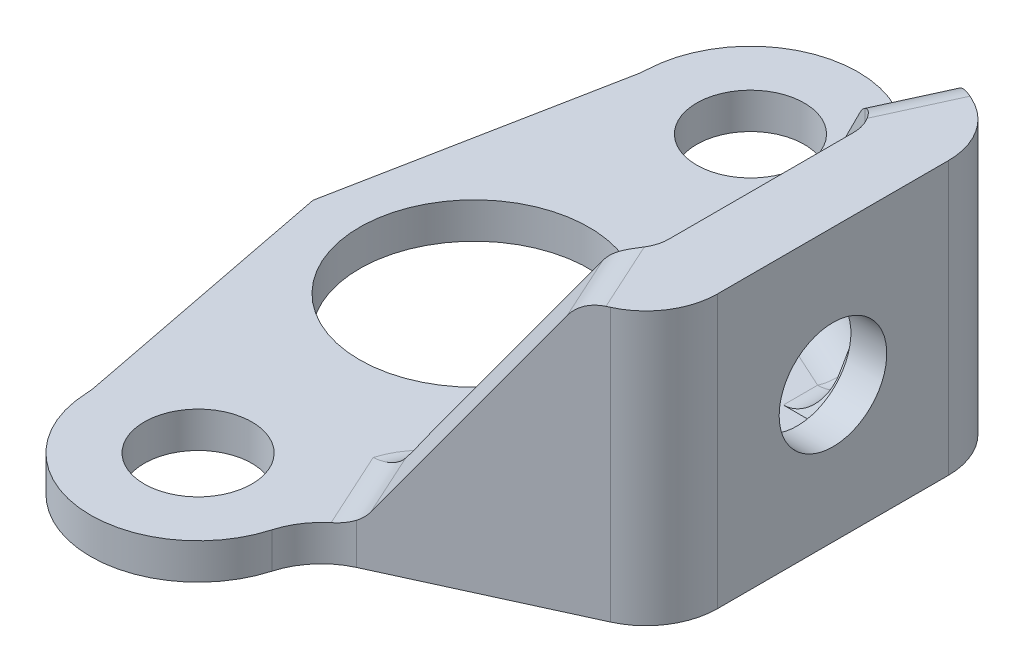
SolidWorks part; units mm, degrees
ref_plane "Plan de face" through (0, 0, 0) normal (0, 0, 1) x (1, 0, 0)
ref_plane "Plan de dessus" through (0, 0, 0) normal (0, 1, 0) x (1, 0, 0)
ref_plane "Plan de droite" through (0, 0, 0) normal (1, 0, 0) x (0, 0, -1)
sketch "Esquisse1" plane through (0, 0, 0) normal (0, 1, 0) x (1, 0, 0)
  line L0 (0, -1000) -> (0, 49000) construction
  line L1 (10, -999.2472) -> (10, 49000.7528) construction
  line L2 (-3.0322, 7.5348) -> (-4.5, 0)
  line L3 (-1000, 4.5) -> (49000, 4.5) construction
  line L4 (3.9764, 7.2537) -> (8.8315, 5.0342)
  line L5 (10, 3.2152) -> (10, -3.2152)
  line L6 (-1000, 0) -> (49000, 0) construction
  line L7 (3.9764, -7.2537) -> (8.8315, -5.0342)
  line L8 (-3.0322, -7.5348) -> (-4.5, 0)
  line L9 (8, 2.5728) -> (8, -2.5728)
  line L10 (7.4158, -3.4823) -> (4.0543, -5.0189)
  line L11 (7.4158, 3.4823) -> (4.0543, 5.0189)
  line L12 (3.9764, 7.2537) -> (3.5606, 6.3442)
  line L13 (3.5606, -6.3442) -> (3.9764, -7.2537)
  circle A0 centre (0, 0) radius 3.2
  circle A1 centre (0, 7.7) radius 1.5
  circle A2 centre (0, 7.7) radius 3 construction
  circle A3 centre (0, 0) radius 4.5 construction
  arc A4 (-2.9972, 7.8303) -> (2.8847, 8.5236) centre (0, 7.7) cw
  arc A5 (-2.9972, 7.8303) -> (-3.0322, 7.5348) centre (-4.9953, 7.9172) cw
  arc A6 (8.8315, 5.0342) -> (10, 3.2152) centre (8, 3.2152) cw
  arc A7 (2.8847, 8.5236) -> (3.9764, 7.2537) centre (4.8079, 9.0726) ccw
  circle A8 centre (0, -7.7) radius 1.5
  arc A9 (8.8315, -5.0342) -> (10, -3.2152) centre (8, -3.2152) ccw
  arc A10 (2.8847, -8.5236) -> (3.9764, -7.2537) centre (4.8079, -9.0726) cw
  arc A11 (-2.9972, -7.8303) -> (2.8847, -8.5236) centre (0, -7.7) ccw
  arc A12 (-2.9972, -7.8303) -> (-3.0322, -7.5348) centre (-4.9953, -7.9172) ccw
  arc A13 (4.0543, -5.0189) -> (3.5606, -6.3442) centre (4.4701, -5.9284) ccw
  arc A14 (8, -2.5728) -> (7.4158, -3.4823) centre (7, -2.5728) cw
  arc A15 (7.4158, 3.4823) -> (8, 2.5728) centre (7, 2.5728) cw
  arc A16 (4.0543, 5.0189) -> (3.5606, 6.3442) centre (4.4701, 5.9284) cw
  point P7 (0, 6.2)
  point P8 (0, 3.2)
  point P24 (10, 4.5)
  point P27 (3, 7.7)
  point P33 (10, 0)
  dimension "D1" = 6.4
  dimension "D3" = 3
  dimension "D4" = 6
  dimension "D5" = 9
  dimension "D7" = 2
  dimension "D9" = 1
  dimension "D2" = 3
  dimension "D6" = 10
  dimension "D8" = 2
extrude "Boss.-Extru.1" add sketch "Esquisse1" against normal blind 1 contours L11 A16 L12 A7 A4 A5 L2 L8 A12 A11 A10 L13 A13 L10 A14 L9 A15 A0 A1 A8 | A16 L11 A15 L9 A14 L10 A13 L13 L7 A9 L5 A6 L4 L12 region at (-2.7631, 0, -7.6528) region at (6.3378, 0, -5.9992)
extrude "Boss.-Extru.2" add sketch "Esquisse1<3>" along normal blind 6.6 contours A16 L11 A15 L9 A14 L10 A13 L13 L7 A9 L5 A6 L4 L12 region at (6.3378, 0, -5.9992)
sketch "Esquisse1<3>" plane through (0, 0, 0) normal (0, 1, 0) x (1, 0, 0) same geometry as "Esquisse1"
chamfer "Chanfrein1" distance 6.6 distance2 4.73 2 edges at (3.7685, 6.6, 6.7989) (3.7685, 6.6, -6.7989) tangent propagation no first distance on face at (3.7685, 3.3, 6.7989) first distance on face at (3.7685, 3.3, -6.7989)
fillet "Congé1" radius 1 9 edges at (7.8623, 6.6, 4.3774) (7.8623, 6.6, -4.3774) (3.7685, 0, 6.7989) (5.7351, 0, 4.2506) (7.8414, 0, 3.1133) (8, 0, 0) (7.8414, 0, -3.1133) (5.7351, 0, -4.2506) (3.7685, 0, -6.7989)
sketch "Esquisse2" plane through (8, 0, 0) normal (-1, 0, 0) x (0, 0, 1)
  line L0 (0, -993.4) -> (0, 49006.6) construction
  line L1 (-2.5728, 6.6) -> (2.5728, 6.6) construction
  line L3 (3.2332, 2.8) -> (1.6166, 5.6)
  line L4 (1.6166, 5.6) -> (-1.6166, 5.6)
  line L5 (-1.6166, 5.6) -> (-3.2332, 2.8)
  line L6 (-3.2332, 2.8) -> (-1.6166, 0)
  line L7 (-1.6166, 0) -> (1.6166, 0)
  line L8 (1.6166, 0) -> (3.2332, 2.8)
  circle A0 centre (0, 2.8) radius 2.8 construction
  circle A1 centre (0, 2.8) radius 1.5
  point P5 (0, 6.6)
  dimension "D3" = 3
  dimension "D1" = 3.8
  dimension "D2" = 5.6
extrude "Enlèv. mat.-Extru.1" cut sketch "Esquisse2" against normal blind 1 and the other way through all contours L6 L7 L8 L3 L4 L5
extrude "Enlèv. mat.-Extru.2" cut sketch "Esquisse2<3>" against normal through all both and the other way through all contours A1 region at (8, 2.8, 0)
sketch "Esquisse2<3>" plane through (8, 0, 0) normal (-1, 0, 0) x (0, 0, 1) same geometry as "Esquisse2"
